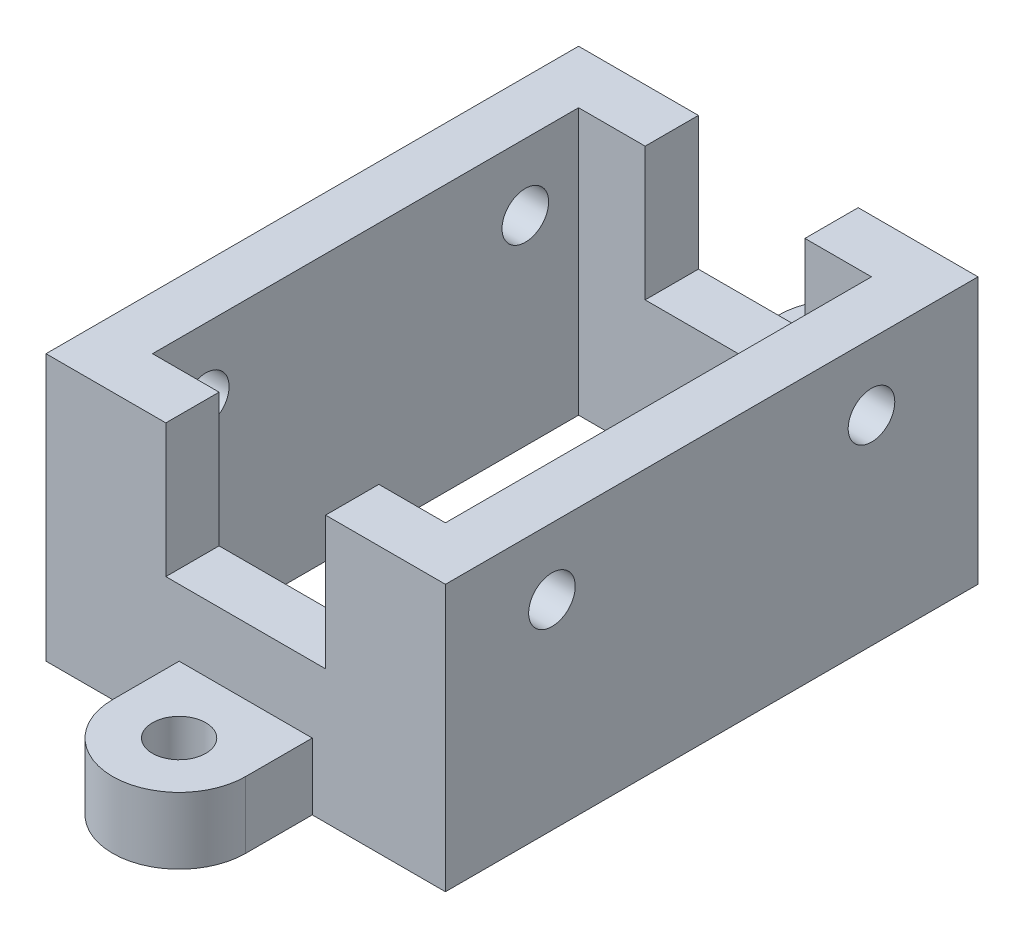
SolidWorks part; units mm, degrees
ref_plane "Plano frontal" through (0, 0, 0) normal (0, 0, 1) x (1, 0, 0)
ref_plane "Plano superior" through (0, 0, 0) normal (0, 1, 0) x (1, 0, 0)
ref_plane "Plano direito" through (0, 0, 0) normal (1, 0, 0) x (0, 0, -1)
sketch "Esboço1" plane through (0, 0, 0) normal (0, 1, 0) x (1, 0, 0)
  line L0 (-15, 20) -> (15, 20)
  line L1 (-11, 16) -> (11, 16)
  line L2 (-11, 16) -> (-11, -16)
  line L3 (-11, -16) -> (11, -16)
  line L4 (11, 16) -> (11, -16)
  line L5 (-11, 16) -> (11, -16) construction
  line L6 (-11, -16) -> (11, 16) construction
  line L7 (15, 20) -> (15, -20)
  line L8 (-15, -20) -> (15, -20)
  line L9 (-15, 20) -> (-15, -20)
  line L10 (-4, 7) -> (4, 7) construction
  line L11 (4, 7) -> (4, 17) construction
  line L12 (4, 17) -> (-4, 17) construction
  line L13 (-4, 17) -> (-4, 7) construction
  line L14 (-11, 0) -> (11, 0) construction
  line L15 (-4, -17) -> (-4, -7) construction
  line L16 (4, -17) -> (-4, -17) construction
  line L17 (4, -7) -> (4, -17) construction
  line L18 (-4, -7) -> (4, -7) construction
  point P0 (0, 0)
  point P12 (0, 7)
  dimension "D2" = 30
  dimension "D3" = 10
  dimension "D4" = 8
  dimension "D5" = 40
  dimension "D6" = 14
  dimension "D1" = 4
extrude "Ressalto-extrusão1" add sketch "Esboço1" along normal blind 20
sketch "Esboço2" plane through (0, 20, 0) normal (0, 1, 0) x (1, 0, 0)
  line L1 (-6, 42.5874) -> (6, 42.5874)
  line L2 (-6, 42.5874) -> (-6, -42.5874)
  line L3 (-6, -42.5874) -> (6, -42.5874)
  line L4 (6, 42.5874) -> (6, -42.5874)
  line L5 (-6, 42.5874) -> (6, -42.5874) construction
  line L6 (-6, -42.5874) -> (6, 42.5874) construction
  point P0 (0, 0)
  dimension "D1" = 12
extrude "Corte-extrusão1" cut sketch "Esboço2" against normal blind 10
sketch "Esboço3" plane through (15, 0, 0) normal (1, 0, 0) x (0, 0, -1)
  line L0 (0, 0) -> (0, 23.3091) construction
  line L1 (-20, 0) -> (20, 0) construction
  line L2 (-12, 15) -> (12, 15) construction
  line L3 (-20, 20) -> (20, 20) construction
  circle A0 centre (-12, 15) radius 1.75
  circle A1 centre (12, 15) radius 1.75
  circle A2 centre (-12, 15) radius 5 construction
  circle A3 centre (12, 15) radius 5 construction
  point P8 (0, 15)
  dimension "D1" = 10
  dimension "D2" = 3.5
  dimension "D3" = 14
  dimension "D4" = 5
extrude "Corte-extrusão2" cut sketch "Esboço3" against normal through all
sketch "Esboço4" plane through (0, 0, 0) normal (0, 1, 0) x (1, 0, 0)
  line L0 (0, 25) -> (0, -25) construction
  line L1 (-5, 25) -> (-5, 20)
  line L2 (6, 20) -> (-6, 20) construction
  line L3 (-5, 20) -> (5, 20)
  line L4 (5, 20) -> (5, 25)
  line L5 (-5, -25) -> (-5, -20)
  line L6 (-6, -20) -> (6, -20) construction
  line L7 (-5, -20) -> (5, -20)
  line L8 (5, -20) -> (5, -25)
  arc A0 (5, 25) -> (-5, 25) centre (0, 25) ccw
  arc A1 (-5, -25) -> (5, -25) centre (0, -25) ccw
  circle A2 centre (0, 25) radius 2
  circle A3 centre (0, -25) radius 2
  point P8 (0, 0)
  dimension "D1" = 10
  dimension "D2" = 4
  dimension "D3" = 50
extrude "Ressalto-extrusão2" add sketch "Esboço4" along normal blind 5
